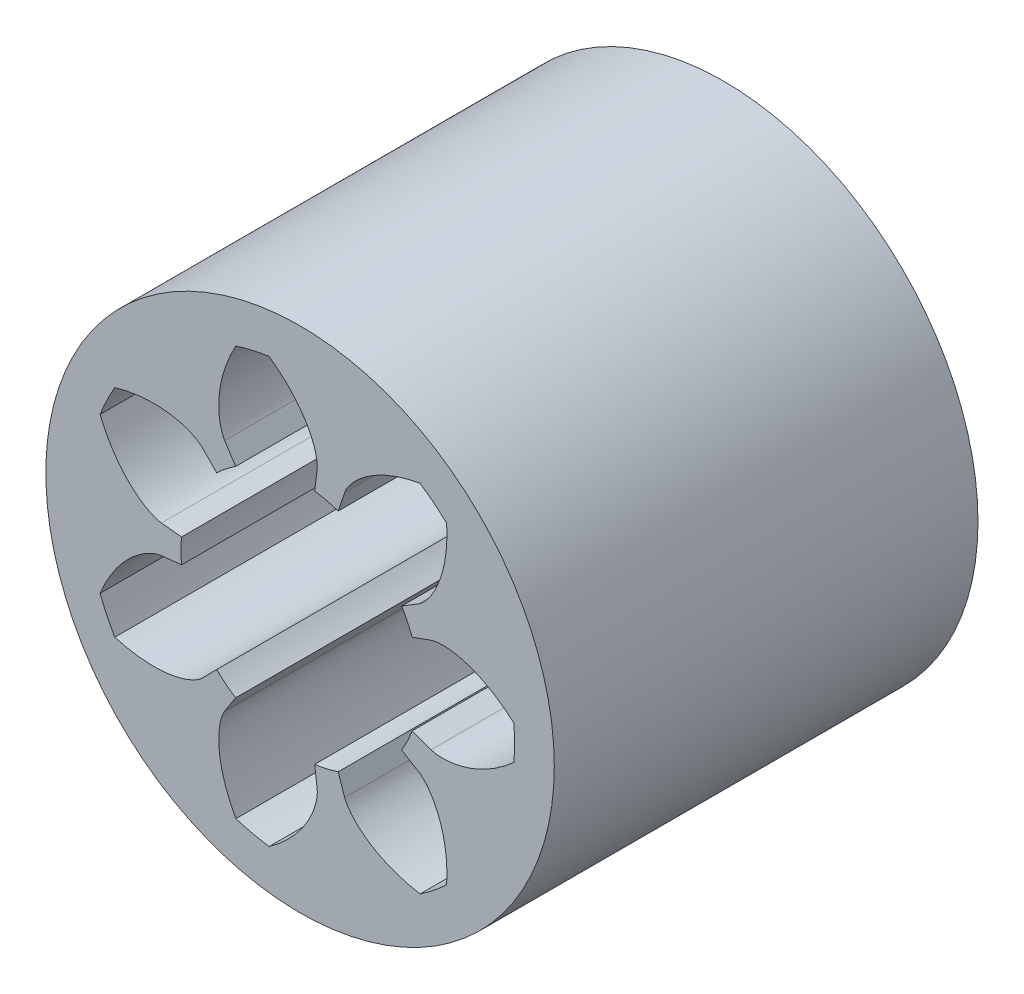
SolidWorks part; units mm, degrees
ref_plane "前视基准面" through (0, 0, 0) normal (0, 0, 1) x (1, 0, 0)
ref_plane "上视基准面" through (0, 0, 0) normal (0, 1, 0) x (1, 0, 0)
ref_plane "右视基准面" through (0, 0, 0) normal (1, 0, 0) x (0, 0, -1)
other "Configuration Table"
sketch "草图1" plane through (0, 0, 0) normal (0, 0, 1) x (1, 0, 0)
  line L0 (0, 0) -> (1.6518, 0.578) construction
  line L1 (0, 0) -> (1.5463, 0.5596)
  line L2 (0, 0) -> (1.5463, -0.5596)
  line L3 (0, 0) -> (1.6518, -0.578) construction
  line L4 (0, 0) -> (2.5312, 0) construction
  line L5 (1.6518, 0.578) -> (1.6518, -0.578) construction
  circle A0 centre (0, 0) radius 1.4062
  circle A1 centre (0, 0) radius 2.5312
  circle A2 centre (0, 0) radius 1.6445 construction
  circle A3 centre (0, 0) radius 1.75 construction
  circle A4 centre (0, 0) radius 3
  spline S0 degree 4 poles (1.5463, 0.5596) (1.5581, 0.5639) (1.5919, 0.5732) (1.6587, 0.581) (1.7677, 0.5785) (1.907, 0.5533) (2.0794, 0.496) (2.2692, 0.3992) (2.4603, 0.2642) (2.6441, 0.0916) (2.8051, -0.1022) (2.943, -0.313) (3.064, -0.5479) (3.1824, -0.853) (3.2764, -1.2324) (3.3196, -1.6847) (3.2901, -2.1883) (3.1874, -2.6826) (3.0209, -3.1576) (2.7922, -3.6086) (2.5154, -4.0264) (2.1841, -4.4125) (1.8255, -4.754) (1.409, -5.0644) (1.076, -5.2702) (0.6819, -5.4662) (0.4502, -5.5624) (0.1823, -5.6645) (0.044, -5.7026) (-0.0764, -5.7409) (-0.1139, -5.7494) (-0.1402, -5.7568) (-0.1543, -5.7609) knots 0 0 0 0 0 0.005604 0.015718 0.02996 0.048734 0.068727 0.096889 0.125051 0.153212 0.181374 0.209535 0.237696 0.271429 0.327752 0.384075 0.440398 0.496721 0.553044 0.609367 0.66569 0.722013 0.778336 0.834659 0.890982 0.909091 0.954545 0.977273 0.988636 0.994318 1 1 1 1 1 construction
  spline S1 degree 4 poles (1.5463, 0.5596) (1.5581, 0.5639) (1.5919, 0.5732) (1.6587, 0.581) (1.7677, 0.5785) (1.907, 0.5533) (2.0794, 0.496) (2.2692, 0.3992) (2.4603, 0.2642) (2.6441, 0.0916) (2.8051, -0.1022) (2.943, -0.313) (3.064, -0.5479) (3.1824, -0.853) (3.2764, -1.2324) (3.3196, -1.6847) (3.2901, -2.1883) (3.1874, -2.6826) (3.0209, -3.1576) (2.7922, -3.6086) (2.5154, -4.0264) (2.1841, -4.4125) (1.8255, -4.754) (1.409, -5.0644) (1.076, -5.2702) (0.7836, -5.4156) (0.6453, -5.4782) (0.6117, -5.493) knots 0 0 0 0 0 0.005604 0.015718 0.02996 0.048734 0.068727 0.096889 0.125051 0.153212 0.181374 0.209535 0.237696 0.271429 0.327752 0.384075 0.440398 0.496721 0.553044 0.609367 0.66569 0.722013 0.778336 0.834659 0.890982 0.909091 0.909091 0.909091 0.909091 0.909091
  spline S2 degree 4 poles (1.5463, -0.5596) (1.5581, -0.5639) (1.5919, -0.5732) (1.6587, -0.581) (1.7677, -0.5785) (1.907, -0.5533) (2.0794, -0.496) (2.2692, -0.3992) (2.4603, -0.2642) (2.6441, -0.0916) (2.8051, 0.1022) (2.943, 0.313) (3.064, 0.5479) (3.1824, 0.853) (3.2764, 1.2324) (3.3196, 1.6847) (3.2901, 2.1883) (3.1874, 2.6826) (3.0209, 3.1576) (2.7922, 3.6086) (2.5154, 4.0264) (2.1841, 4.4125) (1.8255, 4.754) (1.409, 5.0644) (1.076, 5.2702) (0.6819, 5.4662) (0.4502, 5.5624) (0.1823, 5.6645) (0.044, 5.7026) (-0.0764, 5.7409) (-0.1139, 5.7494) (-0.1402, 5.7568) (-0.1543, 5.7609) knots 0 0 0 0 0 0.005604 0.015718 0.02996 0.048734 0.068727 0.096889 0.125051 0.153212 0.181374 0.209535 0.237696 0.271429 0.327752 0.384075 0.440398 0.496721 0.553044 0.609367 0.66569 0.722013 0.778336 0.834659 0.890982 0.909091 0.954545 0.977273 0.988636 0.994318 1 1 1 1 1 construction
  spline S3 degree 4 poles (1.5463, -0.5596) (1.5581, -0.5639) (1.5919, -0.5732) (1.6587, -0.581) (1.7677, -0.5785) (1.907, -0.5533) (2.0794, -0.496) (2.2692, -0.3992) (2.4603, -0.2642) (2.6441, -0.0916) (2.8051, 0.1022) (2.943, 0.313) (3.064, 0.5479) (3.1824, 0.853) (3.2764, 1.2324) (3.3196, 1.6847) (3.2901, 2.1883) (3.1874, 2.6826) (3.0209, 3.1576) (2.7922, 3.6086) (2.5154, 4.0264) (2.1841, 4.4125) (1.8255, 4.754) (1.409, 5.0644) (1.076, 5.2702) (0.7836, 5.4156) (0.6453, 5.4782) (0.6117, 5.493) knots 0 0 0 0 0 0.005604 0.015718 0.02996 0.048734 0.068727 0.096889 0.125051 0.153212 0.181374 0.209535 0.237696 0.271429 0.327752 0.384075 0.440398 0.496721 0.553044 0.609367 0.66569 0.722013 0.778336 0.834659 0.890982 0.909091 0.909091 0.909091 0.909091 0.909091
  point P16 (1.6518, 0)
  dimension "内啮合齿顶圆直径" = 2.8125
  dimension "内啮合分度圆直径" = 3.5
  dimension "内啮合基圆直径" = 3.2889
  dimension "内啮合齿根圆直径" = 5.0625
  dimension "外径" = 6
  dimension "渐开线镜像线夹角" = 19.286
extrude "凸台-拉伸1" add sketch "草图1" along normal blind 5 contours A4 | A0
extrude "切除-拉伸2" cut sketch "草图1<3>" along normal through all contours A0 S3 A1 S1 region at (1.8886, 0, 0)
sketch "草图1<3>" plane through (0, 0, 0) normal (0, 0, 1) x (1, 0, 0) same geometry as "草图1"
pattern_circular "阵列(圆周)1" count 7 over 360 about axis through (0, 0, 5) along (0, 0, 1) of "切除-拉伸2"
equation "\"m\" = 0.5'模数"
equation "\"z1\"= 7'外啮合齿轮数"
equation "\"a\"= 20度'压力角"
equation "\"z2\"= 7'内啮合齿轮数"
equation "\"hax\"= 1'齿顶高系数"
equation "\"cx\"= 0.25'顶隙系数"
equation "\"ha\"= \"hax\" * \"m\"'齿顶高"
equation "\"hf\"= ( \"hax\" + \"cx\" ) * \"m\"'齿根高"
equation "\"d1\"= \"m\" * \"z1\"'外啮合分度圆直径"
equation "\"da1\"= ( \"z1\" + 2 ) * \"m\"'外啮合齿顶圆直径"
equation "\"df1\"= \"d1\" - 2 * \"hf\"'外啮合齿根圆直径"
equation "\"db1\"= \"d1\" * cos ( \"a\" )'外啮合基圆直径"
equation "\"p\"= \"m\" * PI'齿距"
equation "\"d2\"= \"m\" * \"z2\"'内啮合分度圆直径"
equation "\"db2\"= \"d2\" * cos ( \"a\" )'内啮合基圆直径"
equation "\"da2\"= ( \"z2\" - 2 ) * \"m\"'内啮合齿顶圆直径"
equation "\"df2\"= \"d2\" + 2 * \"hf\"'内啮合齿根圆直径"
equation "\"内啮合齿顶圆直径@草图1\" = \"da2\" + 0.5 * \"hf\""
equation "\"内啮合齿根圆直径@草图1\"= \"df2\" + 0.5 * \"hf\""
equation "\"内啮合分度圆直径@草图1\"= \"d2\""
equation "\"内啮合基圆直径@草图1\"= \"db2\""
equation "\"渐开线镜像线夹角@草图1\"= 360度 / 4 / \"z2\" + 360度 / 4 / \"z2\" / 2"
equation "\"do\"= IIF ( \"edo\" >= ( \"df2\" + 1 ) , \"edo\" , ( \"df2\" + 1 ) )'外圈直径"
equation "\"h\"= 5'厚度"
equation "\"外径@草图1\"= \"do\""
equation "\"厚度@凸台-拉伸1\"= \"h\""
equation "\"内啮合齿轮数@阵列(圆周)1\"= \"z2\""
equation "\"edo\"= 6'期望的外圈直径"
